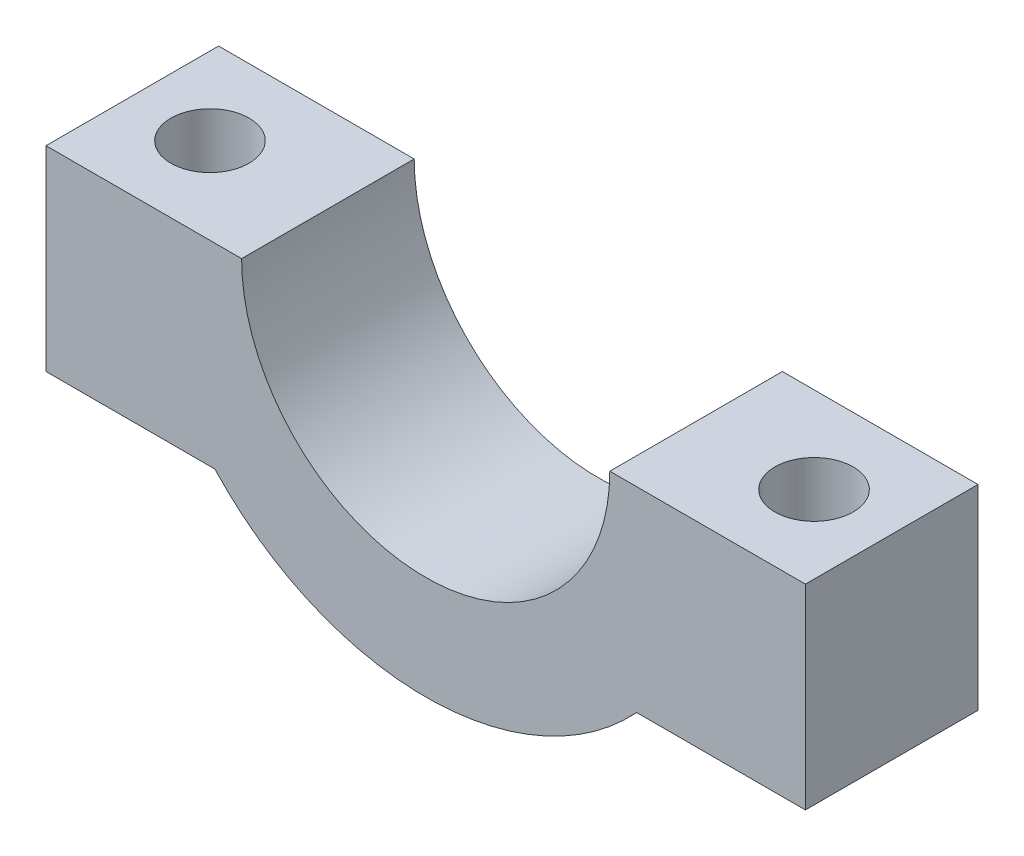
SolidWorks part; units mm, degrees
material "TIMETAL 35A CP Titanium (ASTM Grade 1) 99.1 Ti"
ref_plane "Front Plane" through (0, 0, 0) normal (0, 0, 1) x (1, 0, 0)
ref_plane "Top Plane" through (0, 0, 0) normal (0, 1, 0) x (1, 0, 0)
ref_plane "Right Plane" through (0, 0, 0) normal (1, 0, 0) x (0, 0, -1)
sketch "Sketch1" plane through (0, 0, 0) normal (0, 0, 1) x (1, 0, 0)
  line L1 (-33, 0) -> (-16, 0)
  line L6 (33, 0) -> (16, 0)
  line L7 (33, -17) -> (33, 0)
  line L8 (33, -17) -> (18.3303, -17)
  line L9 (-18.3303, -17) -> (-33, -17)
  line L10 (-33, -17) -> (-33, 0)
  arc A2 (16, 0) -> (-16, 0) centre (0, 0) cw
  arc A3 (18.3303, -17) -> (-18.3303, -17) centre (0, 0) cw
  dimension "D2" = 25
  dimension "D3" = 16
  dimension "D4" = 17
  dimension "D1" = 17
extrude "Boss-Extrude1" add sketch "Sketch1" along normal blind 7.5 and the other way blind 7.5
sketch "Sketch2" plane through (0, -17, 0) normal (0, 1, 0) x (-1, 0, 0)
  circle A0 centre (-26.25, 0) radius 3
  circle A1 centre (26.25, 0) radius 3
  dimension "D1" = 6
  dimension "D2" = 52.5
  dimension "D3" = 26.25
hole_wizard "Tap Drill for M8 Tap1" positions "Sketch3" profile "Sketch4" hole size "M8" standard "ISO" end condition through all
sketch "Sketch3" plane through (0, -17, 0) normal (0, -1, 0) x (-1, 0, 0)
  point P0 (26.25, 0)
  point P3 (-26.25, 0)
sketch "Sketch4" plane through (-26.25, -17, 0) normal (1, 0, 0) x (0, 0, -1)
  line L0 (0, 0) -> (0, 17)
  line L1 (0, 17) -> (3.4, 17)
  line L2 (3.4, 17) -> (3.4, 0)
  line L5 (3.4, 0) -> (0, 0)
  line L11 (0, -6.35) -> (0, 107.95) construction
  dimension "Thru Hole Dia." = 6.8
  dimension "Thru Hole Depth" = 17
equation "\"D3@Sketch2\"=\"D2@Sketch2\"/2"
